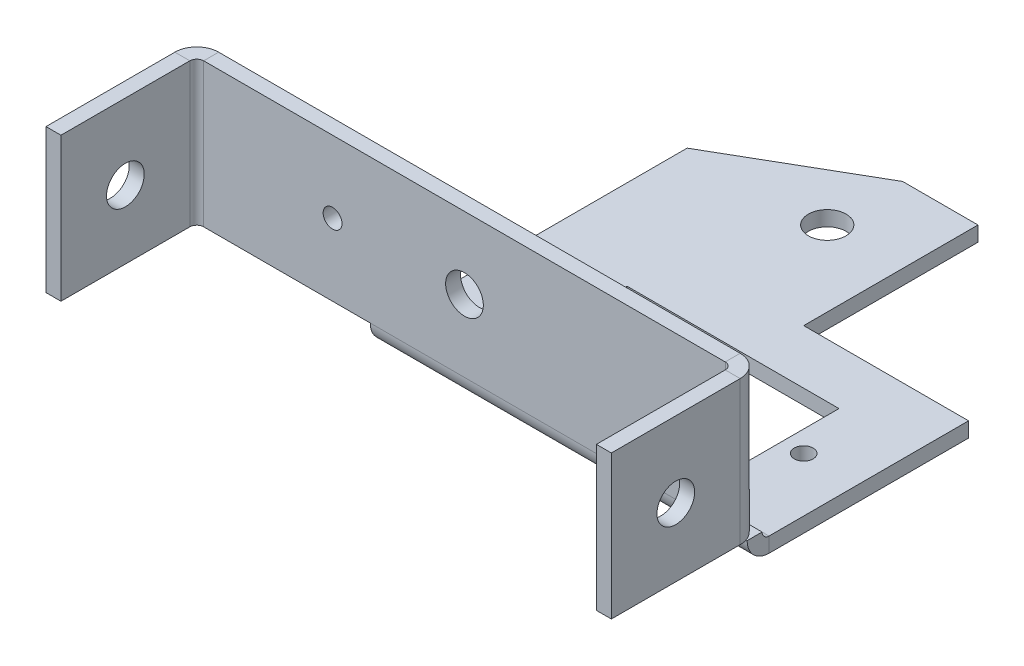
SolidWorks part; units mm, degrees
note: The reader was unsure of these and kept them because the rebuilt part matched: flange length of "Edge-Flange1", "Edge-Flange2".
ref_plane "Front Plane" through (0, 0, 0) normal (0, 0, 1) x (1, 0, 0)
ref_plane "Top Plane" through (0, 0, 0) normal (0, 1, 0) x (1, 0, 0)
ref_plane "Right Plane" through (0, 0, 0) normal (1, 0, 0) x (0, 0, -1)
sketch "Sketch1" plane through (0, 0, 0) normal (0, 1, 0) x (1, 0, 0)
  line L0 (0, 0) -> (17.5, 0)
  line L1 (17.5, 0) -> (17.5, -23.5)
  line L2 (17.5, -23.5) -> (-22.5, -23.5)
  line L3 (-22.5, -23.5) -> (-22.5, 10.1284)
  line L5 (-8, 18.5) -> (0, 18.5)
  line L6 (0, 18.5) -> (0, 0)
  line L7 (-8, 18.5) -> (-22.5, 10.1284)
  line L9 (-13, -5.75) -> (9.5, -5.75)
  line L10 (-13, -5.75) -> (-13, -17.75)
  line L11 (-13, -17.75) -> (9.5, -17.75)
  line L12 (9.5, -5.75) -> (9.5, -17.75)
  line L13 (-13, -5.75) -> (9.5, -17.75) construction
  line L14 (-13, -17.75) -> (9.5, -5.75) construction
  circle A1 centre (-8, 10.5) radius 2
  circle A2 centre (11.75, -11.75) radius 1
  circle A3 centre (-15.25, -11.75) radius 1
  point P12 (-1.75, -11.75)
  point P17 (17.5, -11.75)
  point P22 (-13, -11.75)
  dimension "D7" = 4
  dimension "D9" = 8
  dimension "D15" = 2.25
  dimension "D17" = 2
  dimension "D1" = 40
  dimension "D2" = 22.5
  dimension "D3" = 42
  dimension "D4" = 23.5
  dimension "D5" = 150
  dimension "D6" = 8
  dimension "D10" = 8
  dimension "D12" = 22.5
  dimension "D13" = 12
  dimension "D14" = 5
  dimension "D16" = 2.25
base flange "Base-Flange1" sketch "Sketch1" thickness 1.5875 reverse thickness direction no parameters "D1"=0.7366
edge flange "Edge-Flange1" sketch "Sketch8" flange angle 90 flange length 17.5875 flange position material inside bend radius 0.7366 thickness 1.5875 relief rectangular parameters "D6"=10
sketch "Sketch8" plane through (0, 0, 23.5) normal (0, 0, 1) x (1, 0, 0)
  line L5 (17.5, 16) -> (17.5, 0)
  line L6 (17.5, -1.5875) -> (17.5, 0) construction
  line L7 (17.5, 16) -> (-42.5, 16)
  line L8 (-42.5, 16) -> (-42.5, 0)
  line L9 (-42.5, 0) -> (17.5, 0)
  point P1 (0, 0)
  dimension "D1" = 60
  dimension "D2" = 16
bend "EdgeBend1" bend radius 0.7366 bend angle 90 parameters "D5"=1
sketch "Sketch11" plane through (0, 0, 21.9125) normal (0, 0, -1) x (-1, 0, 0)
  line L0 (-17.5, 16) -> (42.5, 16) construction
  line L1 (42.5, 16) -> (42.5, 0.7366) construction
  circle A1 centre (12.5, 8.3683) radius 2
  circle A2 centre (26.5, 8.3683) radius 1
  point P7 (42.5, 8.3683)
  point P8 (12.5, 16)
  point P12 (0, 0)
  dimension "D1" = 4
  dimension "D2" = 14
  dimension "D3" = 2
extrude "Cut-Extrude1" cut sketch "Sketch11" against normal through all normal cut yes
edge flange "Edge-Flange2" sketch "Sketch14" flange angle 90 flange length 16 flange position material inside bend radius 0.7366 thickness 1.5875 relief none parameters "D6"=10
sketch "Sketch14" plane through (-42.5, 0, 23.5) normal (-1, 0, 0) x (0, -1, 0)
  line L0 (-16, 0) -> (-0.7366, 0) construction
  line L1 (-16, 0) -> (-0.7366, 0)
  line L2 (-16, 0) -> (-16, 14.4125)
  line L3 (-16, 14.4125) -> (-0.7366, 14.4125)
  line L4 (-0.7366, 14.4125) -> (-0.7366, 0)
bend "EdgeBend2" bend radius 0.7366 bend angle 90 parameters "D5"=2
sketch "Sketch15" plane through (-42.5, 0, 0) normal (-1, 0, 0) x (0, 0, 1)
  line L1 (37.9125, 16) -> (24.2366, 16) construction
  circle A0 centre (31.0746, 8) radius 2
  point P3 (31.0746, 16)
  dimension "D3" = 4
  dimension "D2" = 8
extrude "Cut-Extrude2" cut sketch "Sketch15" against normal through all normal cut yes
ref_plane "Plane1" through (-12.5, 0, 0) normal (-1, 0, 0) x (0, 0, 1)
mirror "Mirror1" about plane through (-12.5, 0, 0) normal (-1, 0, 0) of "Edge-Flange2", "Cut-Extrude2"
bend "MirrorBend1" bend radius 0.7366 bend angle 90 parameters "D5"=3
sketch "Bend-Lines1" [suppressed] plane through (0, 0, 0) normal (0, 1, 0) x (1, 0, 0)
sketch "Bounding-Box1" [suppressed] plane through (0, 0, 0) normal (0, 1, 0) x (1, 0, 0)
sheet metal parameters "Sheet-Metal1" thickness 1.5875 parameters "D1"=0.7366
flat pattern "Flat-Pattern1" [suppressed]
sketch "Bend-Lines2" plane through (0, 0, 0) normal (0, 1, 0) x (1, 0, 0)
sketch3d "Bounding-Box2" [suppressed]
  line L0 (-20, -21.5, 0) -> (40, -21.5, 0) construction
  line L1 (-20, 16.5, 0) -> (40, 16.5, 0) construction
  line L2 (-20, -21.5, 0) -> (-20, 16.5, 0) construction
  line L3 (40, -21.5, 0) -> (40, 16.5, 0) construction
sheet metal parameters "Sheet-Metal2" thickness 1.5875 parameters "D1"=0.7366
flat pattern "Flat-Pattern1"
sketch "Bend-Lines2" plane through (0, 0, 0) normal (0, 1, 0) x (1, 0, 0)
  line L0 (-40, -20.3778) -> (-24, -20.3778) construction
  line L1 (-40, -20.3778) -> (-24, -20.3778) construction
sketch3d "Bounding-Box2" [suppressed]
  line L0 (20, -36.8432, 0) -> (-40, -36.8432, 0) construction
  line L1 (20, 16.5, 0) -> (-40, 16.5, 0) construction
  line L2 (20, -36.8432, 0) -> (20, 16.5, 0) construction
  line L3 (-40, -36.8432, 0) -> (-40, 16.5, 0) construction
bend of the flat pattern "Flatten-<EdgeBend1>1"
sheet metal parameters "Sheet-Metal3" thickness 1.5875 parameters "D1"=0.7366
flat pattern "Flat-Pattern1"
sketch "Bend-Lines2" plane through (0, 0, 0) normal (0, 1, 0) x (1, 0, 0)
  line L0 (-40, -20.3778) -> (-24, -20.3778) construction
  line L1 (-40, -20.3778) -> (-24, -20.3778) construction
sketch3d "Bounding-Box2" [suppressed]
  line L0 (20, -36.8432, 0) -> (-40, -36.8432, 0) construction
  line L1 (20, 16.5, 0) -> (-40, 16.5, 0) construction
  line L2 (20, -36.8432, 0) -> (20, 16.5, 0) construction
  line L3 (-40, -36.8432, 0) -> (-40, 16.5, 0) construction
bend of the flat pattern "Flatten-<EdgeBend1>1"
sheet metal parameters "Sheet-Metal4" thickness 1.5875 parameters "D1"=0.7366
flat pattern "Flat-Pattern1"
sketch "Bend-Lines2" plane through (0, 0, 0) normal (0, 1, 0) x (1, 0, 0)
  line L0 (-40, -20.3778) -> (-24, -20.3778) construction
  line L1 (-40, -20.3778) -> (-24, -20.3778) construction
  line L2 (-38.8778, -21.5798) -> (-38.8778, -36.8432) construction
  line L3 (-38.8778, -21.5798) -> (-38.8778, -36.8432) construction
sketch3d "Bounding-Box2" [suppressed]
  line L0 (26.6844, -19.1691, 0) -> (-50.5297, -46.0943, 0) construction
  line L1 (10.9672, 25.9037, 0) -> (-66.247, -1.0215, 0) construction
  line L2 (26.6844, -19.1691, 0) -> (10.9672, 25.9037, 0) construction
  line L3 (-50.5297, -46.0943, 0) -> (-66.247, -1.0215, 0) construction
bend of the flat pattern "Flatten-<EdgeBend1>1"
bend of the flat pattern "Flatten-<EdgeBend2>1"
sheet metal parameters "Sheet-Metal5" thickness 1.5875 parameters "D1"=0.7366
flat pattern "Flat-Pattern1"
sketch "Bend-Lines2" plane through (0, 0, 0) normal (0, 1, 0) x (1, 0, 0)
  line L0 (-25, -20.3778) -> (20, -20.3778) construction
  line L1 (-25, -20.3778) -> (20, -20.3778) construction
  line L2 (-38.8778, -21.5798) -> (-38.8778, -36.8432) construction
  line L3 (-38.8778, -21.5798) -> (-38.8778, -36.8432) construction
sketch3d "Bounding-Box2" [suppressed]
  line L0 (20, -36.8432, 0) -> (-53.7557, -36.8432, 0) construction
  line L1 (20, 18.5, 0) -> (-53.7557, 18.5, 0) construction
  line L2 (20, -36.8432, 0) -> (20, 18.5, 0) construction
  line L3 (-53.7557, -36.8432, 0) -> (-53.7557, 18.5, 0) construction
bend of the flat pattern "Flatten-<EdgeBend1>1"
bend of the flat pattern "Flatten-<EdgeBend2>1"
sheet metal parameters "Sheet-Metal6" thickness 1.5875 parameters "D1"=0.7366
flat pattern "Flat-Pattern1"
sketch "Bend-Lines2" plane through (0, 0, 0) normal (0, 1, 0) x (1, 0, 0)
  line L0 (17.5, -22.3778) -> (-22.5, -22.3778) construction
  line L1 (17.5, -22.3778) -> (-22.5, -22.3778) construction
  line L2 (-41.3778, -23.5798) -> (-41.3778, -38.8432) construction
  line L3 (-41.3778, -23.5798) -> (-41.3778, -38.8432) construction
  line L4 (16.3778, -38.8432) -> (16.3778, -23.5798) construction
  line L5 (16.3778, -38.8432) -> (16.3778, -23.5798) construction
sketch3d "Bounding-Box2" [suppressed]
  line L0 (31.2557, -38.8432, 0) -> (-56.2557, -38.8432, 0) construction
  line L1 (31.2557, 18.5, 0) -> (-56.2557, 18.5, 0) construction
  line L2 (31.2557, -38.8432, 0) -> (31.2557, 18.5, 0) construction
  line L3 (-56.2557, -38.8432, 0) -> (-56.2557, 18.5, 0) construction
bend of the flat pattern "Flatten-<EdgeBend1>1"
bend of the flat pattern "Flatten-<EdgeBend2>1"
bend of the flat pattern "Flatten-<MirrorBend1>1"
